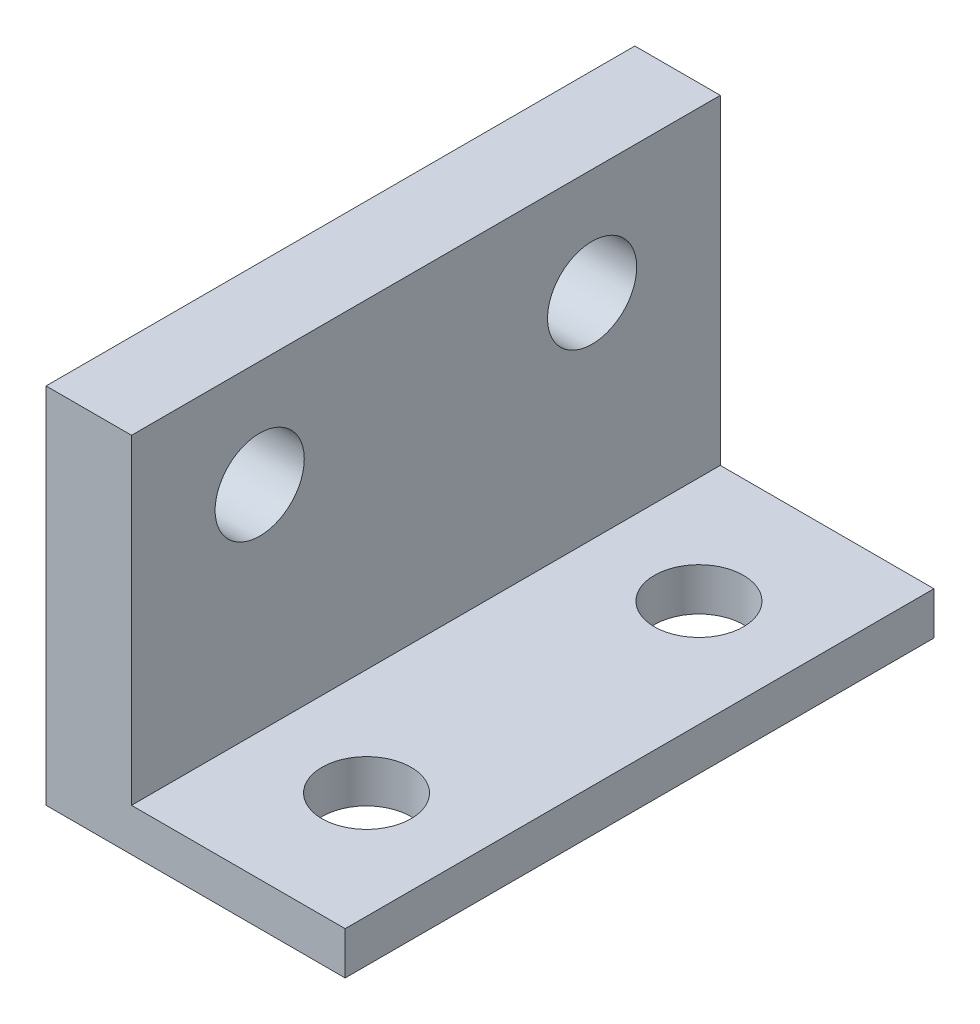
SolidWorks part; units mm, degrees
ref_plane "Front Plane" through (0, 0, 0) normal (0, 0, 1) x (1, 0, 0)
ref_plane "Top Plane" through (0, 0, 0) normal (0, 1, 0) x (1, 0, 0)
ref_plane "Right Plane" through (0, 0, 0) normal (1, 0, 0) x (0, 0, -1)
sketch "Sketch1" plane through (0, 0, 0) normal (0, 0, 1) x (1, 0, 0)
  line L1 (0, 0) -> (17.78, 0)
  line L2 (0, 0) -> (0, 2.54)
  line L3 (0, 2.54) -> (17.78, 2.54)
  line L4 (17.78, 0) -> (17.78, 2.54)
  line L5 (0, 2.54) -> (5.08, 2.54)
  line L6 (0, 2.54) -> (0, 21.59)
  line L7 (0, 21.59) -> (5.08, 21.59)
  line L8 (5.08, 2.54) -> (5.08, 21.59)
  dimension "D1" = 5.08
  dimension "D2" = 12.7
  dimension "D3" = 19.05
  dimension "D4" = 2.54
extrude "Boss-Extrude1" add sketch "Sketch1" along normal blind 35 contours L6 L5 L8 L7 | L2 L1 L4 L3
hole_wizard "Ø5.0mm Dowel Hole1" positions "Sketch2" profile "Sketch3" hole size "Ø5.0" standard "ANSI Metric" end condition through all
sketch "Sketch2" plane through (5.08, 0, 0) normal (1, 0, 0) x (0, 0, -1)
  line L0 (-35, 15.24) -> (0, 15.24) construction
  line L1 (-35, 2.54) -> (-35, 21.59) construction
  line L2 (0, 2.54) -> (0, 21.59) construction
  line L3 (-35, 2.54) -> (0, 2.54) construction
  point P0 (-27.38, 15.24)
  point P2 (-7.62, 15.24)
  dimension "D1" = 7.62
  dimension "D2" = 7.62
  dimension "D3" = 12.7
sketch "Sketch3" plane through (5.08, 15.24, 27.38) normal (0, 1, 0) x (0, 0, -1)
  line L0 (0, 0) -> (0, 5.08)
  line L1 (0, 5.08) -> (2.65, 5.08)
  line L2 (2.65, 5.08) -> (2.65, 0)
  line L5 (2.65, 0) -> (0, 0)
  line L11 (0, -6.35) -> (0, 107.95) construction
  dimension "Thru Hole Dia." = 5.3
  dimension "Thru Hole Depth" = 5.08
hole_wizard "Ø5.0mm Dowel Hole2" positions "Sketch4" profile "Sketch5" hole size "Ø5.0" standard "ANSI Metric" end condition through all
sketch "Sketch4" plane through (0, 2.54, 0) normal (0, 1, 0) x (1, 0, 0)
  line L0 (5.08, 0) -> (17.78, 0) construction
  line L1 (5.08, -35) -> (17.78, -35) construction
  line L2 (11.43, 0) -> (11.43, -35) construction
  point P0 (11.43, -27.38)
  point P2 (11.43, -7.62)
  dimension "D1" = 7.62
  dimension "D2" = 7.62
sketch "Sketch5" plane through (11.43, 2.54, 27.38) normal (1, 0, 0) x (0, 0, 1)
  line L0 (0, 0) -> (0, 2.54)
  line L1 (0, 2.54) -> (2.65, 2.54)
  line L2 (2.65, 2.54) -> (2.65, 0)
  line L5 (2.65, 0) -> (0, 0)
  line L11 (0, -6.35) -> (0, 107.95) construction
  dimension "Thru Hole Dia." = 5.3
  dimension "Thru Hole Depth" = 2.54
equation "\"wall thicc\"= 2.5mm"
equation "\"press fit\"= 0.3mm"
equation "\"shaft thick\"= 5mm + \"press fit\""
equation "\"D1@Sketch1\"=\"wall thicc\"*2"
equation "\"D4@Sketch1\"=\"wall thicc\""
